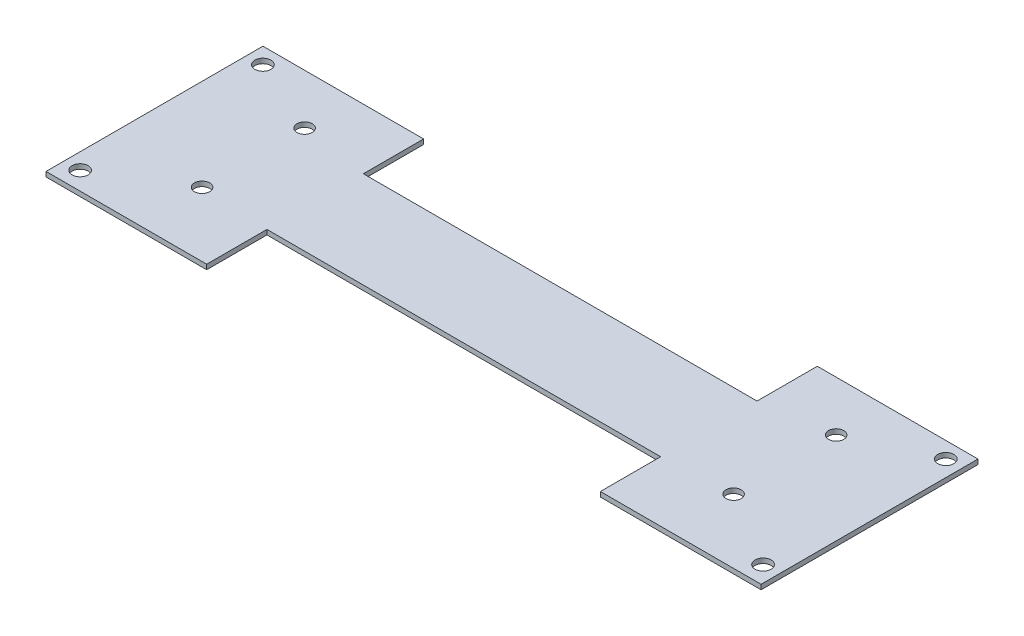
SolidWorks part; units mm, degrees
ref_plane "Front Plane" through (0, 0, 0) normal (0, 0, 1) x (1, 0, 0)
ref_plane "Top Plane" through (0, 0, 0) normal (0, 1, 0) x (1, 0, 0)
ref_plane "Right Plane" through (0, 0, 0) normal (1, 0, 0) x (0, 0, -1)
sketch "Sketch1" plane through (0, 0, 0) normal (0, 1, 0) x (1, 0, 0)
  line L1 (-63.9018, 32.1837) -> (114.0982, 32.1837)
  line L2 (-63.9018, 32.1837) -> (-63.9018, -21.8163)
  line L3 (-63.9018, -21.8163) -> (114.0982, -21.8163)
  line L4 (114.0982, 32.1837) -> (114.0982, -21.8163)
  dimension "D1" = 54
  dimension "D2" = 178
sheet metal parameters "Sheet-Metal1" thickness 1.2 parameters "D1"=0.7366
base flange "Base-Flange1" sketch "Sketch1" thickness 1.2 reverse thickness direction no parameters "D1"=0.7366
sketch "Sketch2" plane through (0, 0, 0) normal (0, 1, 0) x (1, 0, 0)
  line L0 (-63.9018, -21.8163) -> (114.0982, -21.8163) construction
  line L1 (114.0982, -21.8163) -> (114.0982, 32.1837) construction
  circle A0 centre (91.2532, -5.8163) radius 1.9
  circle A1 centre (-41.0568, -5.8163) radius 1.9
  circle A2 centre (91.2532, 19.7137) radius 1.9
  circle A3 centre (-41.0568, 19.7137) radius 1.9
  dimension "D1" = 3.8
  dimension "D2" = 3.8
  dimension "D7" = 3.8
  dimension "D8" = 3.8
  dimension "D3" = 16
  dimension "D4" = 22.845
  dimension "D5" = 16
  dimension "D6" = 132.31
  dimension "D9" = 22.845
  dimension "D10" = 132.31
  dimension "D11" = 25.53
  dimension "D12" = 25.53
extrude "Cut-Extrude1" cut sketch "Sketch2" against normal blind 10 normal cut yes
sketch "Sketch3" plane through (0, 0, 0) normal (0, 1, 0) x (1, 0, 0)
  line L0 (-63.9018, -21.8163) -> (114.0982, -21.8163) construction
  line L1 (74.0982, -21.8163) -> (-23.9018, -21.8163)
  line L2 (74.0982, -21.8163) -> (74.0982, -6.8163)
  line L3 (74.0982, -6.8163) -> (-23.9018, -6.8163)
  line L4 (-23.9018, -21.8163) -> (-23.9018, -6.8163)
  line L5 (114.0982, -21.8163) -> (114.0982, 32.1837) construction
  line L6 (114.0982, 32.1837) -> (-63.9018, 32.1837) construction
  line L8 (74.0982, 32.1837) -> (-23.9018, 32.1837)
  line L9 (74.0982, 32.1837) -> (74.0982, 17.1837)
  line L10 (74.0982, 17.1837) -> (-23.9018, 17.1837)
  line L11 (-23.9018, 32.1837) -> (-23.9018, 17.1837)
  dimension "D1" = 40
  dimension "D2" = 98
  dimension "D3" = 15
  dimension "D4" = 15
  dimension "D5" = 98
  dimension "D6" = 40
extrude "Cut-Extrude2" cut sketch "Sketch3" against normal blind 10 normal cut yes
sketch "Sketch4" plane through (0, 0, 0) normal (0, 1, 0) x (1, 0, 0)
  line L0 (114.0982, -21.8163) -> (114.0982, 32.1837) construction
  line L1 (74.0982, -21.8163) -> (114.0982, -21.8163) construction
  circle A0 centre (110.0982, -17.3163) radius 2
  circle A1 centre (110.0982, 28.1837) radius 2
  dimension "D3" = 4
  dimension "D4" = 4
  dimension "D1" = 4
  dimension "D2" = 4
  dimension "D5" = 4.5
  dimension "D6" = 45.5
extrude "Cut-Extrude3" cut sketch "Sketch4" against normal blind 10 normal cut yes
sketch "Sketch5" plane through (0, 0, 0) normal (0, 1, 0) x (1, 0, 0)
  line L0 (-63.9018, -21.8163) -> (-23.9018, -21.8163) construction
  line L1 (-63.9018, 32.1837) -> (-63.9018, -21.8163) construction
  circle A0 centre (-59.9018, -17.3163) radius 2
  circle A1 centre (-59.9018, 28.1837) radius 2
  dimension "D1" = 4
  dimension "D2" = 4
  dimension "D4" = 4
  dimension "D3" = 4.5
  dimension "D5" = 4
  dimension "D6" = 45.5
extrude "Cut-Extrude4" cut sketch "Sketch5" against normal blind 10 normal cut yes
flat pattern "Flat-Pattern1" [suppressed]
sketch "Bend-Lines1" plane through (0, 0, 0) normal (0, 1, 0) x (1, 0, 0)
sketch3d "Bounding-Box1" [suppressed]
  line L0 (114.0982, -21.8163, 0) -> (-63.9018, -21.8163, 0) construction
  line L1 (114.0982, 32.1837, 0) -> (-63.9018, 32.1837, 0) construction
  line L2 (114.0982, -21.8163, 0) -> (114.0982, 32.1837, 0) construction
  line L3 (-63.9018, -21.8163, 0) -> (-63.9018, 32.1837, 0) construction
